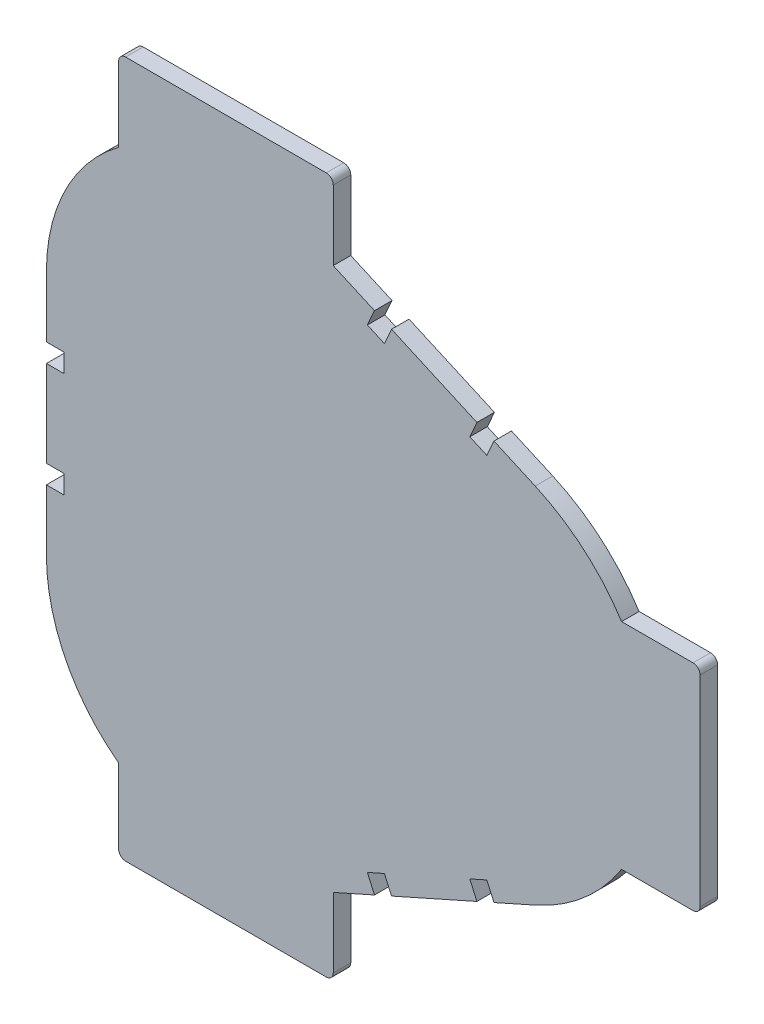
SolidWorks part; units mm, degrees
ref_plane "Front Plane" through (0, 0, 0) normal (0, 0, 1) x (1, 0, 0)
ref_plane "Top Plane" through (0, 0, 0) normal (0, 1, 0) x (1, 0, 0)
ref_plane "Right Plane" through (0, 0, 0) normal (1, 0, 0) x (0, 0, -1)
sketch "Sketch1" plane through (0, 0, -130.81) normal (0, 0, -1) x (-1, 0, 0)
  line L0 (76.8768, 62.4132) -> (76.8768, 49.4592) construction
  line L1 (76.8768, 49.4592) -> (83.2268, 49.4592) construction
  line L2 (83.2268, 49.4592) -> (83.2268, 62.4132) construction
  line L3 (83.2268, 62.4132) -> (76.8768, 62.4132) construction
  line L4 (76.8768, 24.3132) -> (76.8768, 11.3592) construction
  line L5 (76.8768, 11.3592) -> (83.2268, 11.3592) construction
  line L6 (83.2268, 11.3592) -> (83.2268, 24.3132) construction
  line L7 (83.2268, 24.3132) -> (76.8768, 24.3132) construction
  line L8 (83.2268, 52.558) -> (76.8768, 52.558) construction
  line L9 (76.8768, 52.558) -> (76.8768, 21.2144) construction
  line L10 (76.8768, 21.2144) -> (83.2268, 21.2144) construction
  line L11 (83.2268, 21.2144) -> (83.2268, 52.558) construction
  line L12 (-14.4045, -82.987) -> (-14.4045, -59.0193) construction
  line L13 (-15.9112, -56.6989) -> (-33.1241, -49.0339) construction
  line L14 (-33.1241, -49.0339) -> (-35.7072, -54.8347) construction
  line L15 (-35.7072, -54.8347) -> (-20.7545, -61.4933) construction
  line L16 (-20.7545, -61.4933) -> (-20.7545, -86.797) construction
  line L17 (-18.2145, -89.337) -> (54.493, -89.337) construction
  line L18 (57.033, -86.797) -> (57.033, -59.7525) construction
  line L19 (83.2268, -7.5638) -> (83.2268, 14.458) construction
  line L20 (83.2268, 14.458) -> (76.8768, 14.458) construction
  line L21 (76.8768, 14.458) -> (76.8768, -7.5638) construction
  line L22 (50.683, -57.8039) -> (50.683, -82.987) construction
  line L23 (50.683, -82.987) -> (-14.4045, -82.987) construction
  line L24 (-42.127, -45.0248) -> (-44.7101, -50.8256) construction
  line L25 (-44.7101, -50.8256) -> (-32.8764, -56.0953) construction
  line L26 (-32.8764, -56.0953) -> (-30.2932, -50.2945) construction
  line L27 (-30.2932, -50.2945) -> (-42.127, -45.0248) construction
  line L28 (-79.2523, -28.4925) -> (-81.8355, -34.2934) construction
  line L29 (-81.8355, -34.2934) -> (-70.0018, -39.563) construction
  line L30 (-70.0018, -39.563) -> (-67.4186, -33.7622) construction
  line L31 (-67.4186, -33.7622) -> (-79.2523, -28.4925) construction
  line L32 (-39.2961, -46.2854) -> (-70.2494, -32.5016) construction
  line L33 (-70.2494, -32.5016) -> (-72.8326, -38.3024) construction
  line L34 (-72.8326, -38.3024) -> (-41.8793, -52.0862) construction
  line L35 (-41.8793, -52.0862) -> (-39.2961, -46.2854) construction
  line L36 (-125.2661, 75.7799) -> (-151.1873, 75.7799) construction
  line L37 (-153.7273, 73.2399) -> (-153.7273, 0.5324) construction
  line L38 (-151.1873, -2.0076) -> (-125.2661, -2.0076) construction
  line L39 (-93.9575, -28.8953) -> (-79.0047, -35.554) construction
  line L40 (-79.0047, -35.554) -> (-76.4215, -29.7531) construction
  line L41 (-76.4215, -29.7531) -> (-91.3743, -23.0945) construction
  line L42 (-123.1471, 4.3424) -> (-144.8373, 4.3424) construction
  line L43 (-147.3773, 6.8824) -> (-147.3773, 66.8899) construction
  line L44 (-144.8373, 69.4299) -> (-123.1471, 69.4299) construction
  line L45 (-91.3743, 96.8669) -> (-76.4215, 103.5255) construction
  line L46 (-76.4215, 103.5255) -> (-79.0047, 109.3263) construction
  line L47 (-79.0047, 109.3263) -> (-93.9575, 102.6677) construction
  line L48 (-79.2523, 102.2649) -> (-67.4186, 107.5345) construction
  line L49 (-67.4186, 107.5345) -> (-70.0018, 113.3354) construction
  line L50 (-70.0018, 113.3354) -> (-81.8355, 108.0657) construction
  line L51 (-81.8355, 108.0657) -> (-79.2523, 102.2649) construction
  line L52 (-72.8326, 112.0748) -> (-70.2494, 106.274) construction
  line L53 (-70.2494, 106.274) -> (-39.2961, 120.0578) construction
  line L54 (-39.2961, 120.0578) -> (-41.8793, 125.8586) construction
  line L55 (-41.8793, 125.8586) -> (-72.8326, 112.0748) construction
  line L56 (-42.127, 118.7972) -> (-30.2932, 124.0668) construction
  line L57 (-30.2932, 124.0668) -> (-32.8764, 129.8677) construction
  line L58 (-32.8764, 129.8677) -> (-44.7101, 124.598) construction
  line L59 (-44.7101, 124.598) -> (-42.127, 118.7972) construction
  line L60 (-33.1241, 122.8062) -> (-15.9112, 130.4713) construction
  line L61 (-14.4045, 132.7916) -> (-14.4045, 154.2193) construction
  line L62 (-11.8645, 156.7593) -> (48.143, 156.7593) construction
  line L63 (50.683, 154.2193) -> (50.683, 131.5762) construction
  line L64 (76.8768, 81.3362) -> (76.8768, 59.3144) construction
  line L65 (76.8768, 59.3144) -> (83.2268, 59.3144) construction
  line L66 (83.2268, 59.3144) -> (83.2268, 81.3362) construction
  line L67 (57.033, 133.5249) -> (57.033, 160.5693) construction
  line L68 (54.493, 163.1093) -> (-18.2145, 163.1093) construction
  line L69 (-20.7545, 160.5693) -> (-20.7545, 135.2657) construction
  line L70 (-20.7545, 135.2657) -> (-35.7072, 128.6071) construction
  line L71 (-35.7072, 128.6071) -> (-33.1241, 122.8062) construction
  line L72 (76.8768, 62.4132) -> (76.8768, 49.4592)
  line L73 (76.8768, 49.4592) -> (83.2268, 49.4592)
  line L74 (83.2268, 49.4592) -> (83.2268, 62.4132)
  line L75 (83.2268, 62.4132) -> (76.8768, 62.4132)
  line L76 (76.8768, 24.3132) -> (76.8768, 11.3592)
  line L77 (76.8768, 11.3592) -> (83.2268, 11.3592)
  line L78 (83.2268, 11.3592) -> (83.2268, 24.3132)
  line L79 (83.2268, 24.3132) -> (76.8768, 24.3132)
  line L80 (83.2268, 52.558) -> (76.8768, 52.558)
  line L81 (76.8768, 52.558) -> (76.8768, 21.2144)
  line L82 (76.8768, 21.2144) -> (83.2268, 21.2144)
  line L83 (83.2268, 21.2144) -> (83.2268, 52.558)
  line L84 (-14.4045, -82.987) -> (-14.4045, -59.0193)
  line L85 (-15.9112, -56.6989) -> (-33.1241, -49.0339)
  line L86 (-33.1241, -49.0339) -> (-35.7072, -54.8347)
  line L87 (-35.7072, -54.8347) -> (-20.7545, -61.4933)
  line L88 (-20.7545, -61.4933) -> (-20.7545, -86.797)
  line L89 (-18.2145, -89.337) -> (54.493, -89.337)
  line L90 (57.033, -86.797) -> (57.033, -59.7525)
  line L91 (83.2268, -7.5638) -> (83.2268, 14.458)
  line L92 (83.2268, 14.458) -> (76.8768, 14.458)
  line L93 (76.8768, 14.458) -> (76.8768, -7.5638)
  line L94 (50.683, -57.8039) -> (50.683, -82.987)
  line L95 (50.683, -82.987) -> (-14.4045, -82.987)
  line L96 (-42.127, -45.0248) -> (-44.7101, -50.8256)
  line L97 (-44.7101, -50.8256) -> (-32.8764, -56.0953)
  line L98 (-32.8764, -56.0953) -> (-30.2932, -50.2945)
  line L99 (-30.2932, -50.2945) -> (-42.127, -45.0248)
  line L100 (-79.2523, -28.4925) -> (-81.8355, -34.2934)
  line L101 (-81.8355, -34.2934) -> (-70.0018, -39.563)
  line L102 (-70.0018, -39.563) -> (-67.4186, -33.7622)
  line L103 (-67.4186, -33.7622) -> (-79.2523, -28.4925)
  line L104 (-39.2961, -46.2854) -> (-70.2494, -32.5016)
  line L105 (-70.2494, -32.5016) -> (-72.8326, -38.3024)
  line L106 (-72.8326, -38.3024) -> (-41.8793, -52.0862)
  line L107 (-41.8793, -52.0862) -> (-39.2961, -46.2854)
  line L108 (-125.2661, 75.7799) -> (-151.1873, 75.7799)
  line L109 (-153.7273, 73.2399) -> (-153.7273, 0.5324)
  line L110 (-151.1873, -2.0076) -> (-125.2661, -2.0076)
  line L111 (-93.9575, -28.8953) -> (-79.0047, -35.554)
  line L112 (-79.0047, -35.554) -> (-76.4215, -29.7531)
  line L113 (-76.4215, -29.7531) -> (-91.3743, -23.0945)
  line L114 (-123.1471, 4.3424) -> (-144.8373, 4.3424)
  line L115 (-147.3773, 6.8824) -> (-147.3773, 66.8899)
  line L116 (-144.8373, 69.4299) -> (-123.1471, 69.4299)
  line L117 (-91.3743, 96.8669) -> (-76.4215, 103.5255)
  line L118 (-76.4215, 103.5255) -> (-79.0047, 109.3263)
  line L119 (-79.0047, 109.3263) -> (-93.9575, 102.6677)
  line L120 (-79.2523, 102.2649) -> (-67.4186, 107.5345)
  line L121 (-67.4186, 107.5345) -> (-70.0018, 113.3354)
  line L122 (-70.0018, 113.3354) -> (-81.8355, 108.0657)
  line L123 (-81.8355, 108.0657) -> (-79.2523, 102.2649)
  line L124 (-72.8326, 112.0748) -> (-70.2494, 106.274)
  line L125 (-70.2494, 106.274) -> (-39.2961, 120.0578)
  line L126 (-39.2961, 120.0578) -> (-41.8793, 125.8586)
  line L127 (-41.8793, 125.8586) -> (-72.8326, 112.0748)
  line L128 (-42.127, 118.7972) -> (-30.2932, 124.0668)
  line L129 (-30.2932, 124.0668) -> (-32.8764, 129.8677)
  line L130 (-32.8764, 129.8677) -> (-44.7101, 124.598)
  line L131 (-44.7101, 124.598) -> (-42.127, 118.7972)
  line L132 (-33.1241, 122.8062) -> (-15.9112, 130.4713)
  line L133 (-14.4045, 132.7916) -> (-14.4045, 154.2193)
  line L134 (-11.8645, 156.7593) -> (48.143, 156.7593)
  line L135 (50.683, 154.2193) -> (50.683, 131.5762)
  line L136 (76.8768, 81.3362) -> (76.8768, 59.3144)
  line L137 (76.8768, 59.3144) -> (83.2268, 59.3144)
  line L138 (83.2268, 59.3144) -> (83.2268, 81.3362)
  line L139 (57.033, 133.5249) -> (57.033, 160.5693)
  line L140 (54.493, 163.1093) -> (-18.2145, 163.1093)
  line L141 (-20.7545, 160.5693) -> (-20.7545, 135.2657)
  line L142 (-20.7545, 135.2657) -> (-35.7072, 128.6071)
  line L143 (-35.7072, 128.6071) -> (-33.1241, 122.8062)
  arc A0 (-14.4045, -59.0193) -> (-15.9112, -56.6989) centre (-16.9445, -59.0193) ccw construction
  arc A1 (-20.7545, -86.797) -> (-18.2145, -89.337) centre (-18.2145, -86.797) ccw construction
  arc A2 (54.493, -89.337) -> (57.033, -86.797) centre (54.493, -86.797) ccw construction
  arc A3 (57.033, -59.7525) -> (83.2268, -7.5638) centre (18.1393, -7.5638) ccw construction
  arc A4 (51.7688, -55.7214) -> (76.8768, -7.5638) centre (18.1393, -7.5638) ccw construction
  arc A5 (51.7688, -55.7214) -> (50.683, -57.8039) centre (53.223, -57.8039) ccw construction
  arc A6 (-151.1873, 75.7799) -> (-153.7273, 73.2399) centre (-151.1873, 73.2399) ccw construction
  arc A7 (-153.7273, 0.5324) -> (-151.1873, -2.0076) centre (-151.1873, 0.5324) ccw construction
  arc A8 (-125.2661, -2.0076) -> (-93.9575, -28.8953) centre (-64.6643, 36.8862) ccw construction
  arc A9 (-120.969, 3.1091) -> (-91.3743, -23.0945) centre (-64.6643, 36.8862) ccw construction
  arc A10 (-120.969, 3.1091) -> (-123.1471, 4.3424) centre (-123.1471, 1.8024) ccw construction
  arc A11 (-147.3773, 6.8824) -> (-144.8373, 4.3424) centre (-144.8373, 6.8824) ccw construction
  arc A12 (-144.8373, 69.4299) -> (-147.3773, 66.8899) centre (-144.8373, 66.8899) ccw construction
  arc A13 (-123.1471, 69.4299) -> (-120.969, 70.6633) centre (-123.1471, 71.9699) ccw construction
  arc A14 (-91.3743, 96.8669) -> (-120.969, 70.6633) centre (-64.6643, 36.8862) ccw construction
  arc A15 (-93.9575, 102.6677) -> (-125.2661, 75.7799) centre (-64.6643, 36.8862) ccw construction
  arc A16 (-15.9112, 130.4713) -> (-14.4045, 132.7916) centre (-16.9445, 132.7916) ccw construction
  arc A17 (-11.8645, 156.7593) -> (-14.4045, 154.2193) centre (-11.8645, 154.2193) ccw construction
  arc A18 (50.683, 154.2193) -> (48.143, 156.7593) centre (48.143, 154.2193) ccw construction
  arc A19 (50.683, 131.5762) -> (51.7688, 129.4937) centre (53.223, 131.5762) ccw construction
  arc A20 (76.8768, 81.3362) -> (51.7688, 129.4937) centre (18.1393, 81.3362) ccw construction
  arc A21 (83.2268, 81.3362) -> (57.033, 133.5249) centre (18.1393, 81.3362) ccw construction
  arc A22 (57.033, 160.5693) -> (54.493, 163.1093) centre (54.493, 160.5693) ccw construction
  arc A23 (-18.2145, 163.1093) -> (-20.7545, 160.5693) centre (-18.2145, 160.5693) ccw construction
  arc A24 (-14.4045, -59.0193) -> (-15.9112, -56.6989) centre (-16.9445, -59.0193) ccw
  arc A25 (-20.7545, -86.797) -> (-18.2145, -89.337) centre (-18.2145, -86.797) ccw
  arc A26 (54.493, -89.337) -> (57.033, -86.797) centre (54.493, -86.797) ccw
  arc A27 (57.033, -59.7525) -> (83.2268, -7.5638) centre (18.1393, -7.5638) ccw
  arc A28 (51.7688, -55.7214) -> (76.8768, -7.5638) centre (18.1393, -7.5638) ccw
  arc A29 (51.7688, -55.7214) -> (50.683, -57.8039) centre (53.223, -57.8039) ccw
  arc A30 (-151.1873, 75.7799) -> (-153.7273, 73.2399) centre (-151.1873, 73.2399) ccw
  arc A31 (-153.7273, 0.5324) -> (-151.1873, -2.0076) centre (-151.1873, 0.5324) ccw
  arc A32 (-125.2661, -2.0076) -> (-93.9575, -28.8953) centre (-64.6643, 36.8862) ccw
  arc A33 (-120.969, 3.1091) -> (-91.3743, -23.0945) centre (-64.6643, 36.8862) ccw
  arc A34 (-120.969, 3.1091) -> (-123.1471, 4.3424) centre (-123.1471, 1.8024) ccw
  arc A35 (-147.3773, 6.8824) -> (-144.8373, 4.3424) centre (-144.8373, 6.8824) ccw
  arc A36 (-144.8373, 69.4299) -> (-147.3773, 66.8899) centre (-144.8373, 66.8899) ccw
  arc A37 (-123.1471, 69.4299) -> (-120.969, 70.6633) centre (-123.1471, 71.9699) ccw
  arc A38 (-91.3743, 96.8669) -> (-120.969, 70.6633) centre (-64.6643, 36.8862) ccw
  arc A39 (-93.9575, 102.6677) -> (-125.2661, 75.7799) centre (-64.6643, 36.8862) ccw
  arc A40 (-15.9112, 130.4713) -> (-14.4045, 132.7916) centre (-16.9445, 132.7916) ccw
  arc A41 (-11.8645, 156.7593) -> (-14.4045, 154.2193) centre (-11.8645, 154.2193) ccw
  arc A42 (50.683, 154.2193) -> (48.143, 156.7593) centre (48.143, 154.2193) ccw
  arc A43 (50.683, 131.5762) -> (51.7688, 129.4937) centre (53.223, 131.5762) ccw
  arc A44 (76.8768, 81.3362) -> (51.7688, 129.4937) centre (18.1393, 81.3362) ccw
  arc A45 (83.2268, 81.3362) -> (57.033, 133.5249) centre (18.1393, 81.3362) ccw
  arc A46 (57.033, 160.5693) -> (54.493, 163.1093) centre (54.493, 160.5693) ccw
  arc A47 (-18.2145, 163.1093) -> (-20.7545, 160.5693) centre (-18.2145, 160.5693) ccw
  line M24 (-125.2661, 75.7799) -> (-151.1873, 75.7799)
  arc M25 (-151.1873, 75.7799) -> (-153.7273, 73.2399) centre (-151.1873, 73.2399) ccw
  line M26 (-153.7273, 73.2399) -> (-153.7273, 0.5324)
  arc M27 (-153.7273, 0.5324) -> (-151.1873, -2.0076) centre (-151.1873, 0.5324) ccw
  line M28 (-151.1873, -2.0076) -> (-125.2661, -2.0076)
  arc M29 (-125.2661, -2.0076) -> (-93.9575, -28.8953) centre (-64.6643, 36.8862) ccw
  line M30 (-93.9575, -28.8953) -> (-79.0047, -35.554)
  line M31 (-79.0047, -35.554) -> (-76.4215, -29.7531)
  line M32 (-76.4215, -29.7531) -> (-91.3743, -23.0945)
  arc M33 (-91.3743, -23.0945) -> (-120.969, 3.1091) centre (-64.6643, 36.8862) cw
  arc M34 (-120.969, 3.1091) -> (-123.1471, 4.3424) centre (-123.1471, 1.8024) ccw
  line M35 (-123.1471, 4.3424) -> (-144.8373, 4.3424)
  arc M36 (-144.8373, 4.3424) -> (-147.3773, 6.8824) centre (-144.8373, 6.8824) cw
  line M37 (-147.3773, 6.8824) -> (-147.3773, 66.8899)
  arc M38 (-147.3773, 66.8899) -> (-144.8373, 69.4299) centre (-144.8373, 66.8899) cw
  line M39 (-144.8373, 69.4299) -> (-123.1471, 69.4299)
  arc M40 (-123.1471, 69.4299) -> (-120.969, 70.6633) centre (-123.1471, 71.9699) ccw
  arc M41 (-120.969, 70.6633) -> (-91.3743, 96.8669) centre (-64.6643, 36.8862) cw
  line M42 (-91.3743, 96.8669) -> (-76.4215, 103.5255)
  line M43 (-76.4215, 103.5255) -> (-79.0047, 109.3263)
  line M44 (-79.0047, 109.3263) -> (-93.9575, 102.6677)
  arc M45 (-93.9575, 102.6677) -> (-125.2661, 75.7799) centre (-64.6643, 36.8862) ccw
extrude "Boss-Extrude1" add sketch "Sketch1" along normal blind 6.35 contours L136 A44 A43 L135 A42 L134 A41 L133 A40 L132 L128 L125 L120 L117 L103 L104 L99 L85 A24 L84 L95 L94 A29 A28 L93 L76 L81 L72 M42 M41 M40 M39 M38 M37 M36 M35 M34 M33 M32 | L72 L137 L74 L75 | L140 A47 L141 L142 L129 L132 A40 L133 A41 L134 A42 L135 A43 A44 L136 L75 L138 A45 L139 A46 | L74 L80 L72 L73 | L79 L83 L73 L81 | L76 L82 L78 L79 | L78 L92 L76 L77 | A28 A29 L94 L95 L84 A24 L85 L98 L87 L88 A25 L89 A26 L90 A27 L91 L77 L93 | L87 L98 L85 L86 | L97 L107 L99 L96 | L102 L106 L96 L104 | L103 L105 L101 L102 | L123 L119 L100 M45 M24 M25 M26 M27 M28 M29 M30 M32 M33 M34 M35 M36 M37 M38 M39 M40 M41 M42 | L100 M32 M30 M31 | L131 L127 L121 L125 | L127 L131 L125 L126 | L130 L143 L128 L129 | L122 L124 L120 L121 | L123 L117 M44 M43 region at (-80.0518, 60.8638, -130.81) region at (-78.4137, 71.8747, -130.81) region at (16.28, 36.8771, -130.81) region at (-80.0518, 51.0086, -130.81) region at (-80.0518, 36.8862, -130.81) region at (-80.0518, 22.7638, -130.81) region at (-80.0518, 12.9086, -130.81) region at (-80.0518, 9.8223, -130.81) region at (33.0002, 126.337, -130.81) region at (42.0031, 122.3279, -130.81) region at (56.0644, 116.0663, -130.81) region at (70.1256, 109.8047, -130.81) region at (33.0002, -52.5646, -130.81) region at (79.1285, 105.7956, -130.81) region at (82.0116, 104.5117, -130.81) region at (42.0031, -48.5555, -130.81) region at (56.0644, -42.2939, -130.81) region at (70.1256, -36.0323, -130.81) region at (79.1285, -32.0232, -130.81)
